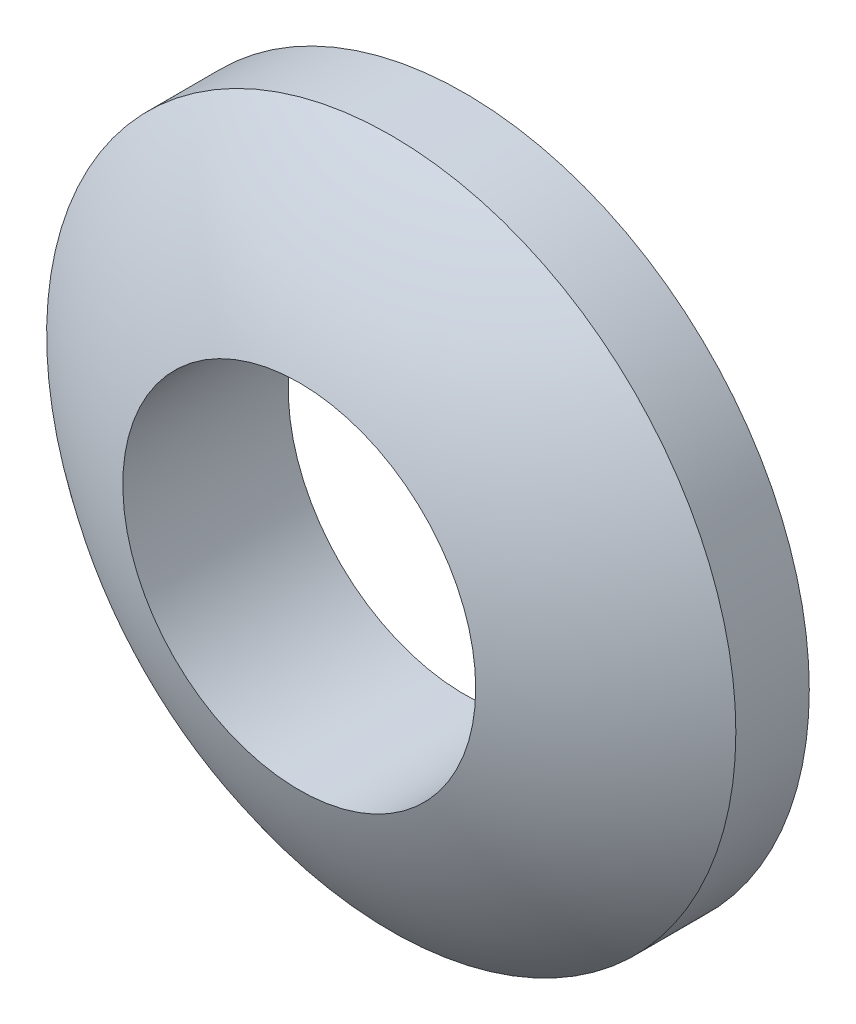
SolidWorks part; units mm, degrees
ref_plane "Front" through (0, 0, 0) normal (0, 0, 1) x (1, 0, 0)
ref_plane "Top" through (0, 0, 0) normal (0, 1, 0) x (1, 0, 0)
ref_plane "Right" through (0, 0, 0) normal (1, 0, 0) x (0, 0, -1)
sketch "Sketch1" plane through (0, 0, 0) normal (-1, 0, 0) x (0, -1, 0)
  line L0 (-3.2, -3) -> (-6.25, -3)
  line L1 (-6.25, -3) -> (-6.25, -1.6679)
  line L2 (0, 58.0501) -> (0, -42.8594) construction
  line L3 (-3.2, -3) -> (-3.2, 0)
  arc A0 (-3.2, 0) -> (-6.25, -1.6679) centre (0, -9.4742) ccw
  dimension "SR" = 10
  dimension "D0" = 12.5
  dimension "h" = 3
  dimension "d" = 6.4
revolve "Base-Revolve" add sketch "Sketch1" angle 360 about L2
